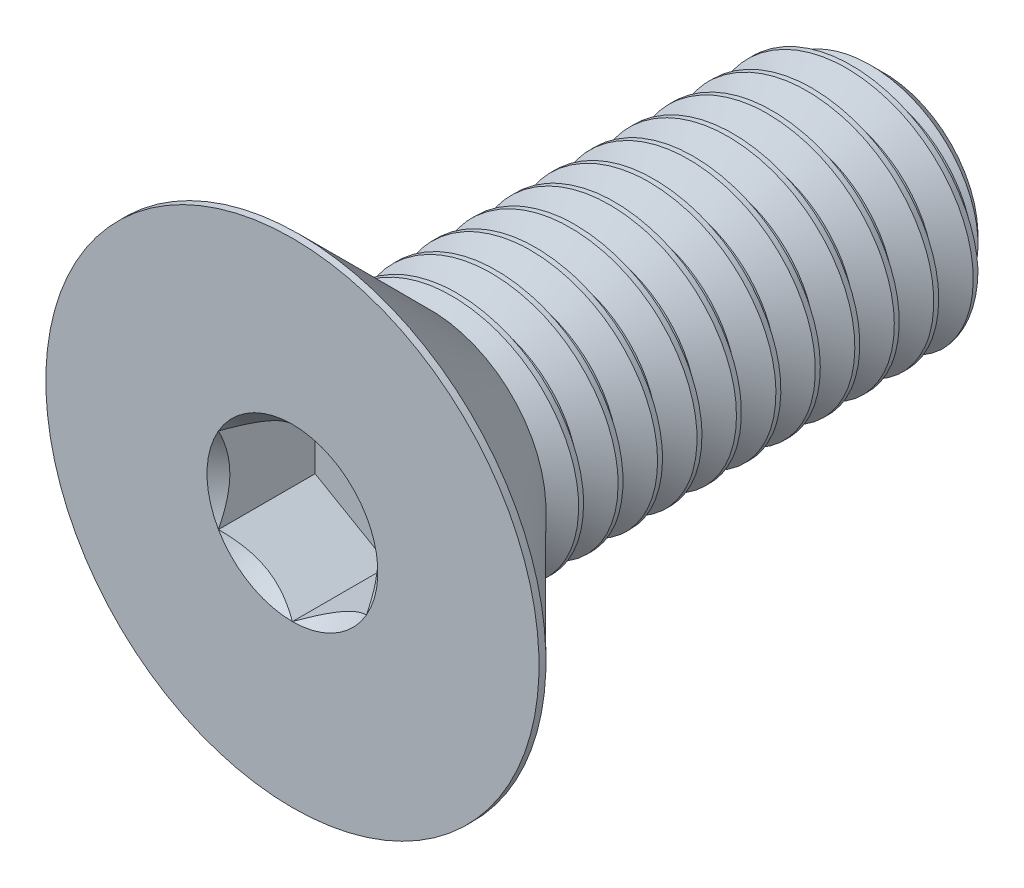
SolidWorks part; units mm, degrees
ref_plane "Front" through (0, 0, 0) normal (0, 0, 1) x (1, 0, 0)
ref_plane "Top" through (0, 0, 0) normal (0, 1, 0) x (1, 0, 0)
ref_plane "Right" through (0, 0, 0) normal (1, 0, 0) x (0, 0, -1)
sketch "Sketch11" plane through (0, 0, 0) normal (1, 0, 0) x (0, 0, -1)
  line L0 (-6, 5) -> (6, 5) construction
  line L5 (-6, 5) -> (-6, -5) construction
  line L6 (6, 2.5) -> (6, -2.5) construction
  line L7 (-5.99, 1.5) -> (-5.99, -1.5) construction
  line L8 (5.95, 2.5866) -> (6.75, 2.5866) construction
  line L9 (6.75, 2.5866) -> (6.35, 1.8938) construction
  line L10 (6.35, 1.8938) -> (5.95, 2.5866) construction
  line L11 (6.3, 1.9804) -> (6.4, 1.9804) construction
  line L12 (6.35, 1.9804) -> (6.35, 1.8938) construction
  line L13 (5.975, 2.5433) -> (6.725, 2.5433) construction
  line L14 (6.35, 2.5866) -> (6.35, 2.5) construction
  line L15 (6, 2.5) -> (6.7, 2.5) construction
  line L17 (-5.86, 5) -> (-0.86, 0) construction
  line L18 (-0.86, 0) -> (-5.86, -5) construction
  point P3 (-3.2, 5)
  point P8 (0, 5)
  point P21 (6.35, 2.5433)
  point P26 (-6, 0)
  point P28 (-5.99, 0)
  point P29 (6, 0)
  dimension "Length" = 12
  dimension "Head Diameter" = 10
  dimension "Thread Major Diameter" = 5
  dimension "Head Height" = 2.8
  dimension "Drive Size" = 3
  dimension "Thread Pitch" = 0.8
  dimension "D1" = 0.1
  dimension "D2" = 0.01
  dimension "D3" = 0.14
  dimension "Countersink Angle" = 90
sketch "Sketch1" plane through (0, 0, 0) normal (1, 0, 0) x (0, 0, -1)
  line L2 (-3.2, 2.5) -> (6, 2.5)
  line L3 (6, 2.5) -> (6, 0)
  line L4 (-4.04, 2.5) -> (-4.04, 0)
  line L5 (-3.2, 2.5) -> (-4.04, 2.5)
  line L6 (-6, 5) -> (-6, -5) construction
  line L7 (6, 2.5) -> (6, -2.5) construction
  line L8 (-4.04, 0) -> (6, 0)
  dimension "D1" = 1.96
revolve "Revolve1" add sketch "Sketch1" angle 360 mid plane about L8
chamfer "Chamfer1" distance 0.6 angle 45 1 edges at (0, -2.5, -6)
sketch "Sketch7" plane through (0, 0, 0) normal (1, 0, 0) x (0, 0, -1)
  line L2 (-6, 5) -> (-5.86, 5)
  line L5 (-3.2, 2.34) -> (-3.2, 0)
  line L6 (-6, 5) -> (-6, 0)
  line L8 (-6, 5) -> (-6, -5) construction
  line L9 (-6, 0) -> (-3.2, 0)
  line L12 (-5.86, 5) -> (-3.2, 2.34)
  line L13 (-5.86, 5) -> (-0.86, 0) construction
revolve "Revolve2" add sketch "Sketch7" angle 360 mid plane about L9 region at (0, 1.9545, 4.7736)
ref_plane "Plane1" through (0, 0, 3.2) normal (0, 0, 1) x (1, 0, 0)
sketch "Sketch5" plane through (0, 0, 6) normal (0, 0, 1) x (1, 0, 0)
  line L1 (1.5, -0.866) -> (1.5, 0.866)
  line L2 (1.5, 0.866) -> (0, 1.7321)
  line L3 (0, 1.7321) -> (-1.5, 0.866)
  line L4 (-1.5, 0.866) -> (-1.5, -0.866)
  line L5 (-1.5, -0.866) -> (0, -1.7321)
  line L6 (0, -1.7321) -> (1.5, -0.866)
  circle A0 centre (0, 0) radius 1.5 construction
extrude "Cut-Extrude2" cut sketch "Sketch5" against normal blind 1.96
sketch "Sketch6" plane through (0, 0, 6) normal (0, 0, -1) x (-1, 0, 0)
  circle A0 centre (0, 0) radius 1.7321
extrude "Cut-Extrude3" cut sketch "Sketch6" along normal blind 1.96 draft 45
sketch "Sketch12" plane through (0, 0, -6) normal (0, 0, -1) x (-1, 0, 0)
  circle A0 centre (0, 0) radius 2.5 construction
  circle A1 centre (0, 0) radius 2.5
curve "Helix/Spiral1" pitch 0.8 height 12 radius 2.5 centre (0, 0, -6) axis (0, 0, 1) start towards (0, 1, 0)
sketch "Sketch13" plane through (0, 0, 0) normal (1, 0, 0) x (0, 0, -1)
  line L0 (5.975, 2.5433) -> (6.725, 2.5433)
  line L1 (6.725, 2.5433) -> (6.4, 1.9804)
  line L2 (6.4, 1.9804) -> (6.3, 1.9804)
  line L3 (6.3, 1.9804) -> (5.975, 2.5433)
sweep "Cut-Sweep1" cut profiles "Sketch13" path "Helix/Spiral1" align with end faces yes
combine bodies "Combine1" operation type add bodies to combine 113 127
equation "\"D1@Chamfer1\"=\"Thread Pitch@Sketch11\" * .75"
equation "\"D1@Cut-Extrude2\"= \"Head Height@Sketch11\" * .7"
equation "\"D1@Cut-Extrude3\" = \"D1@Cut-Extrude2\""
equation "\"D1@Sketch11\"=\"Thread Pitch@Sketch11\"/8"
equation "\"D3@Sketch11\"=\"Head Height@Sketch11\"*.05"
equation "\"D4@Helix/Spiral1\"=\"Thread Pitch@Sketch11\""
equation "\"D1@Sketch1\"=\"Head Height@Sketch11\"*.7"
equation "\"D3@Helix/Spiral1\"=\"Length@Sketch11\""
